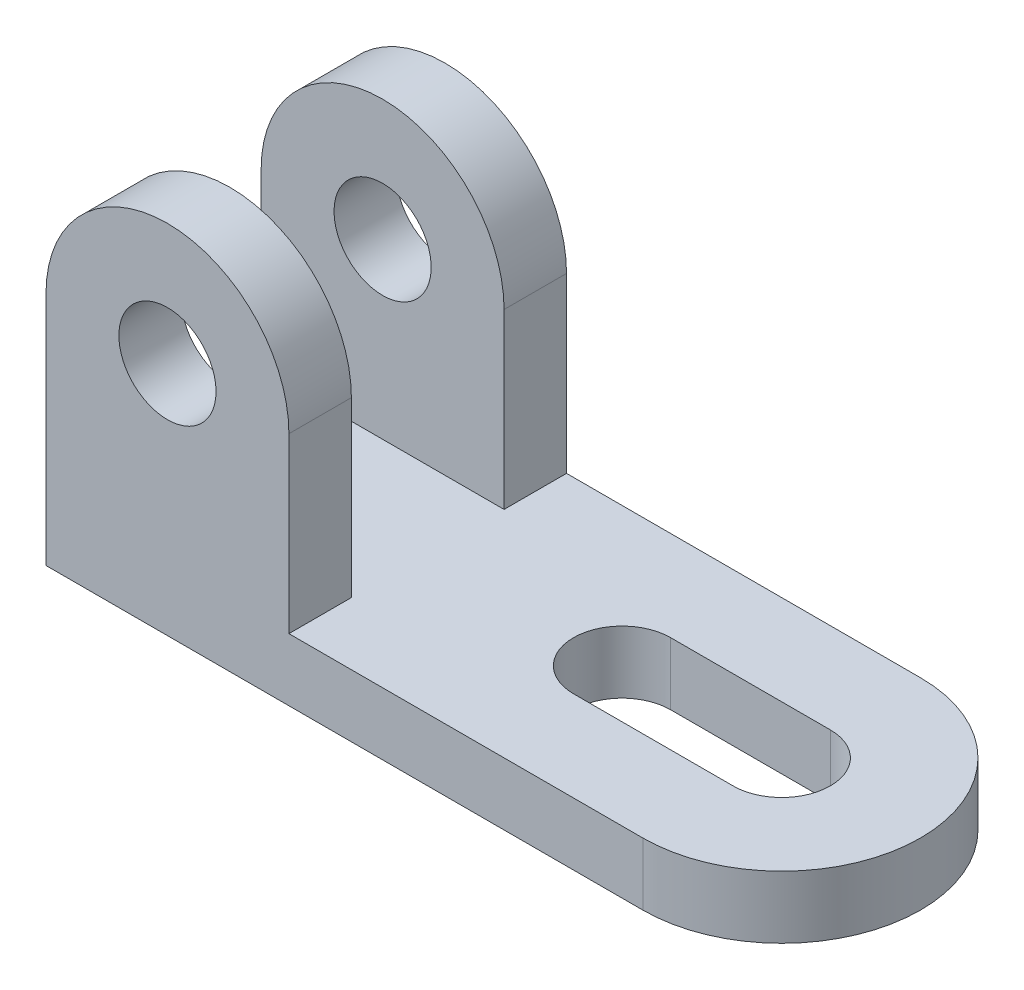
SolidWorks part; units mm, degrees
ref_plane "Front Plane" through (0, 0, 0) normal (0, 0, 1) x (1, 0, 0)
ref_plane "Top Plane" through (0, 0, 0) normal (0, 1, 0) x (1, 0, 0)
ref_plane "Right Plane" through (0, 0, 0) normal (1, 0, 0) x (0, 0, -1)
sketch "Sketch2" plane through (0, 0, 0) normal (0, 1, 0) x (1, 0, 0)
  line L0 (-105.7331, 0) -> (24.4508, 0) construction
  line L1 (-98.0511, 20) -> (-12.0511, 20)
  line L2 (-98.0511, -20) -> (-12.0511, -20)
  line L3 (-12.0511, 0) -> (-35.0511, 0) construction
  line L4 (-12.0511, -7) -> (-35.0511, -7)
  line L5 (-12.0511, 7) -> (-35.0511, 7)
  line L6 (-98.0511, 20) -> (-98.0511, -20)
  line L7 (-98.0511, 11) -> (-63.0511, 11)
  line L8 (-63.0511, 11) -> (-63.0511, 20)
  line L9 (-63.0511, -11) -> (-63.0511, -20)
  line L10 (-98.0511, -11) -> (-63.0511, -11)
  arc A0 (-12.0511, -20) -> (-12.0511, 20) centre (-12.0511, 0) ccw
  arc A2 (-12.0511, -7) -> (-12.0511, 7) centre (-12.0511, 0) ccw
  arc A3 (-35.0511, 7) -> (-35.0511, -7) centre (-35.0511, 0) ccw
  point P9 (-23.5511, 0)
  dimension "D1" = 40
  dimension "D2" = 23
  dimension "D3" = 14
  dimension "D4" = 86
  dimension "D5" = 35
  dimension "D6" = 9
extrude "Boss-Extrude1" add sketch "Sketch2" along normal blind 9 contours L2 A0 L1 L8 L7 L6 L10 L9 A3 L5 A2 L4 region at (-43.7683, 0, 0)
extrude "Boss-Extrude2" add sketch "Sketch2<3>" along normal blind 55.5 contours L10 L6 L2 L9 | L7 L8 L1 L6 region at (-80.5511, 0, -15.5) region at (-80.5511, 0, 15.5)
sketch "Sketch2<3>" plane through (0, 0, 0) normal (0, 1, 0) x (1, 0, 0) same geometry as "Sketch2"
sketch "Sketch3" plane through (0, 0, 20) normal (0, 0, 1) x (1, 0, 0)
  line L0 (-111.5721, 33.9477) -> (-47.689, 33.9477) construction
  line L1 (-63.0511, 33.9477) -> (-63.0511, 55.5)
  line L2 (-63.0511, 55.5) -> (-98.0511, 55.5)
  line L3 (-98.0511, 55.5) -> (-98.0511, 33.9477)
  line L4 (-98.0511, 33.9477) -> (-63.0511, 33.9477)
  arc A1 (-63.0511, 33.9477) -> (-98.0511, 33.9477) centre (-80.5511, 33.9477) ccw
  circle A2 centre (-80.5511, 33.9477) radius 7
  line M6 (-63.0511, 9) -> (-63.0511, 55.5)
  line M7 (-63.0511, 55.5) -> (-98.0511, 55.5)
  line M8 (-98.0511, 55.5) -> (-98.0511, 0)
  dimension "D2" = 35
extrude "Cut-Extrude1" cut sketch "Sketch3" against normal blind 55.5 contours A1 M6 M7 M8 | L4 A2 | L4 A2 region at (-80.5511, 51.8587, 20) region at (-80.5511, 30.9768, 20) region at (-80.5511, 36.9186, 20)
